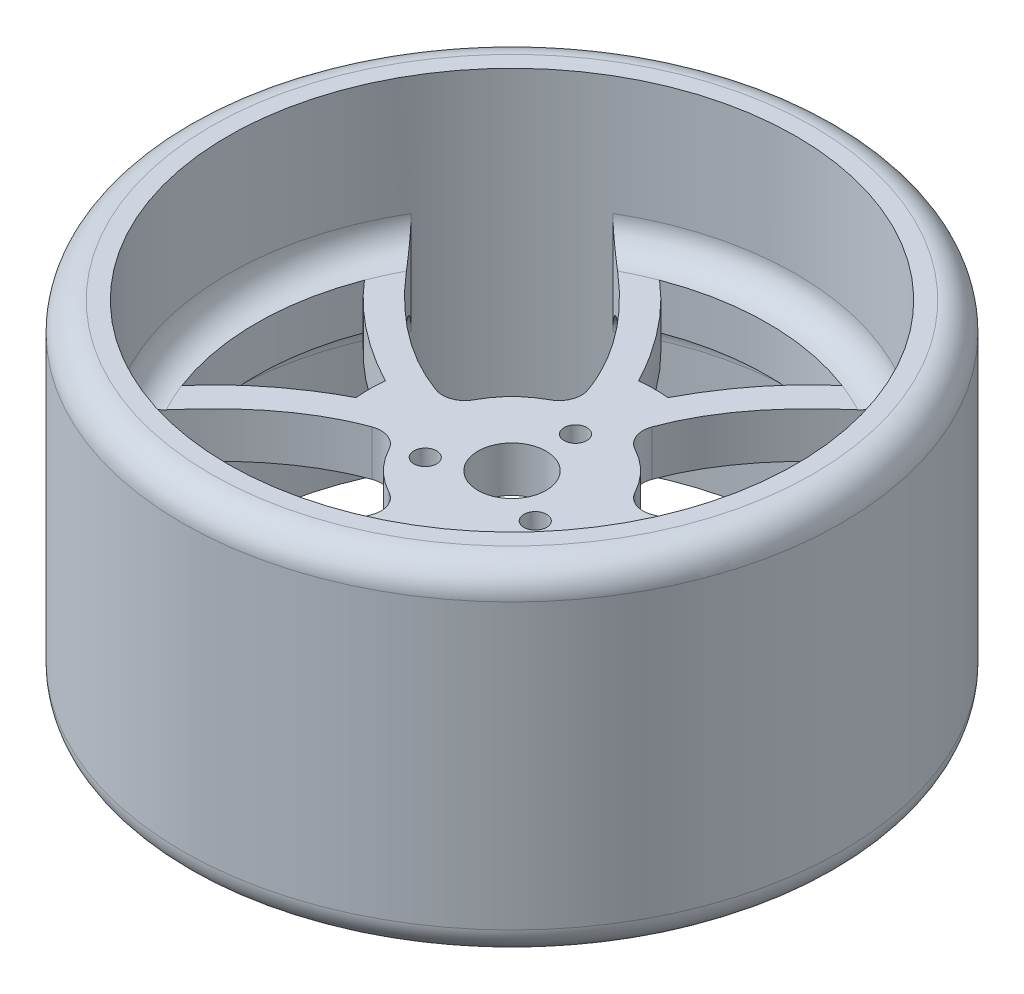
SolidWorks part; units mm, degrees
ref_plane "Front Plane" through (0, 0, 0) normal (0, 0, 1) x (1, 0, 0)
ref_plane "Top Plane" through (0, 0, 0) normal (0, 1, 0) x (1, 0, 0)
ref_plane "Right Plane" through (0, 0, 0) normal (1, 0, 0) x (0, 0, -1)
sketch "Sketch1" plane through (0, 0, 0) normal (0, 1, 0) x (1, 0, 0)
  circle A0 centre (0, 0) radius 3
  circle A1 centre (0, 0) radius 8
  dimension "D1" = 6
  dimension "D2" = 16
extrude "Boss-Extrude1" add sketch "Sketch1" along normal mid plane 4
sketch "Sketch2" plane through (0, 0, 0) normal (0, 1, 0) x (1, 0, 0)
  line L0 (0, 25) -> (0, -25) construction
  line L1 (-25, 0) -> (25, 0) construction
  arc A2 (2.2696, 7.6713) -> (-2.2696, 7.6713) centre (0, 0) ccw
  arc A3 (12.6709, 21.5511) -> (-12.6709, 21.5511) centre (0, 0) ccw
  circle A4 centre (0, 0) radius 25 construction
  arc A5 (7.6713, -2.2696) -> (7.6713, 2.2696) centre (0, 0) ccw
  arc A6 (21.5511, -12.6709) -> (21.5511, 12.6709) centre (0, 0) ccw
  arc A7 (-2.2696, -7.6713) -> (2.2696, -7.6713) centre (0, 0) ccw
  arc A8 (-12.6709, -21.5511) -> (12.6709, -21.5511) centre (0, 0) ccw
  arc A9 (-7.6713, 2.2696) -> (-7.6713, -2.2696) centre (0, 0) ccw
  arc A10 (-21.5511, 12.6709) -> (-21.5511, -12.6709) centre (0, 0) ccw
  circle A11 centre (0, 0) radius 22.5 construction
  circle A12 centre (0, 0) radius 12.5 construction
  arc A14 (1.2819, 12.4341) -> (-1.2819, 12.4341) centre (0, 0) ccw
  arc A15 (8.0302, 21.0182) -> (-8.0302, 21.0182) centre (0, 0) ccw
  arc A16 (21.0182, -8.0302) -> (21.0182, 8.0302) centre (0, 0) ccw
  arc A17 (12.4341, -1.2819) -> (12.4341, 1.2819) centre (0, 0) ccw
  arc A18 (-8.0302, -21.0182) -> (8.0302, -21.0182) centre (0, 0) ccw
  arc A19 (-1.2819, -12.4341) -> (1.2819, -12.4341) centre (0, 0) ccw
  arc A20 (-21.0182, 8.0302) -> (-21.0182, -8.0302) centre (0, 0) ccw
  arc A21 (-12.4341, 1.2819) -> (-12.4341, -1.2819) centre (0, 0) ccw
  spline S0 degree 2 poles (-12.6709, 21.5511) (-4.0139, 15.0092) (-2.2696, 7.6713) knots 0 0 0 0.242244 0.242244 0.242244
  spline S1 degree 2 poles (12.6709, 21.5511) (4.0139, 15.0092) (2.2696, 7.6713) knots 0 0 0 0.242244 0.242244 0.242244
  spline S2 degree 2 poles (21.5511, 12.6709) (15.0092, 4.0139) (7.6713, 2.2696) knots 0 0 0 0.242244 0.242244 0.242244
  spline S3 degree 2 poles (21.5511, -12.6709) (15.0092, -4.0139) (7.6713, -2.2696) knots 0 0 0 0.242244 0.242244 0.242244
  spline S4 degree 2 poles (12.6709, -21.5511) (4.0139, -15.0092) (2.2696, -7.6713) knots 0 0 0 0.242244 0.242244 0.242244
  spline S5 degree 2 poles (-12.6709, -21.5511) (-4.0139, -15.0092) (-2.2696, -7.6713) knots 0 0 0 0.242244 0.242244 0.242244
  spline S6 degree 2 poles (-21.5511, -12.6709) (-15.0092, -4.0139) (-7.6713, -2.2696) knots 0 0 0 0.242244 0.242244 0.242244
  spline S7 degree 2 poles (-21.5511, 12.6709) (-15.0092, 4.0139) (-7.6713, 2.2696) knots 0 0 0 0.242244 0.242244 0.242244
  spline S8 degree 2 poles (1.2819, 12.4341) (3.9986, 17.5696) (8.0302, 21.0182) knots 0 0 0 0.407977 0.407977 0.407977
  spline S9 degree 2 poles (-1.2819, 12.4341) (-3.9986, 17.5696) (-8.0302, 21.0182) knots 0 0 0 0.407977 0.407977 0.407977
  spline S10 degree 2 poles (12.4341, 1.2819) (17.5696, 3.9986) (21.0182, 8.0302) knots 0 0 0 0.407977 0.407977 0.407977
  spline S11 degree 2 poles (12.4341, -1.2819) (17.5696, -3.9986) (21.0182, -8.0302) knots 0 0 0 0.407977 0.407977 0.407977
  spline S12 degree 2 poles (1.2819, -12.4341) (3.9986, -17.5696) (8.0302, -21.0182) knots 0 0 0 0.407977 0.407977 0.407977
  spline S13 degree 2 poles (-1.2819, -12.4341) (-3.9986, -17.5696) (-8.0302, -21.0182) knots 0 0 0 0.407977 0.407977 0.407977
  spline S14 degree 2 poles (-12.4341, -1.2819) (-17.5696, -3.9986) (-21.0182, -8.0302) knots 0 0 0 0.407977 0.407977 0.407977
  spline S15 degree 2 poles (-12.4341, 1.2819) (-17.5696, 3.9986) (-21.0182, 8.0302) knots 0 0 0 0.407977 0.407977 0.407977
  point P27 (0, 0)
  point P46 (0, 0)
  dimension "D1" = 8
  dimension "D2" = 25
  dimension "D3" = 17.6933
  dimension "D5" = 45
  dimension "D6" = 25
  dimension "D7" = 17.6933
  dimension "D4" = 4
  dimension "D8" = 4
extrude "Boss-Extrude2" add sketch "Sketch2" along normal mid plane 4
sketch "Sketch3" plane through (0, 0, 0) normal (0, 1, 0) x (1, 0, 0)
  circle A0 centre (0, 0) radius 25
  circle A1 centre (0, 0) radius 29
  dimension "D2" = 58
  dimension "D3" = 50
extrude "Boss-Extrude3" add sketch "Sketch3" along normal mid plane 30
fillet "Fillet4" radius 2 8 edges at (2.2696, 0, -7.6713) (7.6713, 0, -2.2696) (2.2696, 0, 7.6713) (7.6713, 0, 2.2696) (-2.2696, 0, 7.6713) (-7.6713, 0, 2.2696) (-7.6713, 0, -2.2696) (-2.2696, 0, -7.6713)
fillet "Fillet5" radius 2.5 4 edges at (0, 2, 25) (25, 2, 0) (0, 2, -25) (-25, 2, 0)
fillet "Fillet6" radius 2.5 4 edges at (0, -2, -25) (-25, -2, 0) (0, -2, 25) (25, -2, 0)
fillet "Fillet7" radius 2.5 2 edges at (0, -15, 29) (0, 15, 29)
sketch "Sketch4" plane through (0, 0, 0) normal (0, 1, 0) x (1, 0, 0)
  circle A0 centre (0, 0) radius 3.0888 construction
  circle A1 centre (0, 0) radius 8 construction
  circle A2 centre (0, 0) radius 5.5888 construction
  circle A3 centre (0, 5.5888) radius 1
  circle A7 centre (4.8401, -2.7944) radius 1
  circle A8 centre (-4.8401, -2.7944) radius 1
  point P13 (0, 0)
  point P16 (0, 0)
  dimension "D1" = 2.5
  dimension "D2" = 2
  dimension "D3" = 3
extrude "Cut-Extrude1" cut sketch "Sketch4" against normal mid plane 4
